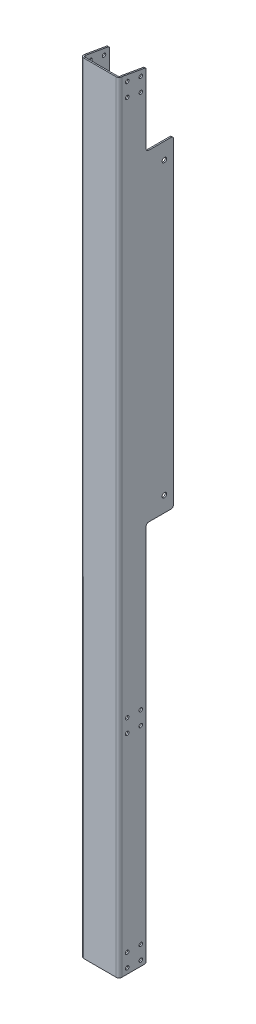
SolidWorks part; units mm, degrees
note: The reader was unsure of these and kept them because the rebuilt part matched: flange length of "Edge-Flange1", "Edge-Flange2".
ref_plane "Front Plane" through (0, 0, 0) normal (0, 0, 1) x (1, 0, 0)
ref_plane "Top Plane" through (0, 0, 0) normal (0, 1, 0) x (1, 0, 0)
ref_plane "Right Plane" through (0, 0, 0) normal (1, 0, 0) x (0, 0, -1)
sketch "Sketch1" plane through (0, 0, 0) normal (0, 0, 1) x (1, 0, 0)
  line L1 (26.6776, 546.1) -> (-26.6776, 546.1)
  line L2 (26.6776, 546.1) -> (26.6776, -546.1)
  line L3 (26.6776, -546.1) -> (-26.6776, -546.1)
  line L4 (-26.6776, 546.1) -> (-26.6776, -546.1)
  line L5 (26.6776, 546.1) -> (-26.6776, -546.1) construction
  line L6 (26.6776, -546.1) -> (-26.6776, 546.1) construction
  point P0 (0, 0)
  dimension "D1" = 53.3552
  dimension "D2" = 1092.2
base flange "Base-Flange1" sketch "Sketch1" thickness 1.8974 reverse thickness direction no parameters "D1"=2.032
edge flange "Edge-Flange1" sketch "Sketch8" flange angle 90 flange length 76.2 flange position material inside bend radius 2.032 thickness 1.8974 relief rectangular parameters "D6"=10
sketch "Sketch8" plane through (26.6776, 0, -1.8974) normal (-1, 0, 0) x (0, 1, 0)
  line L0 (546.1, 2.8778) -> (540.2239, 36.2026)
  line L2 (-546.1, 0) -> (-546.1, 36.2026)
  line L3 (-546.1, 36.2026) -> (-15.875, 36.2026)
  line L4 (546.1, 2.8778) -> (546.1, 0)
  line L5 (546.1, 0) -> (-546.1, 0) construction
  line L6 (546.1, 0) -> (-546.1, 0)
  line L7 (438.15, 39.3776) -> (438.15, 71.1276)
  line L8 (434.975, 74.3026) -> (-9.525, 74.3026)
  line L9 (-12.7, 71.1276) -> (-12.7, 39.3776)
  line L10 (441.325, 36.2026) -> (540.2239, 36.2026)
  line L11 (546.1, -1.8974) -> (-546.1, -1.8974) construction
  arc A0 (-12.7, 39.3776) -> (-15.875, 36.2026) centre (-15.875, 39.3776) cw
  arc A1 (438.15, 39.3776) -> (441.325, 36.2026) centre (441.325, 39.3776) ccw
  arc A2 (-9.525, 74.3026) -> (-12.7, 71.1276) centre (-9.525, 71.1276) ccw
  arc A3 (438.15, 71.1276) -> (434.975, 74.3026) centre (434.975, 71.1276) ccw
  point P17 (438.15, 36.2026)
  dimension "D7" = 3.175
  dimension "D8" = 3.175
  dimension "D9" = 3.175
  dimension "D10" = 3.175
  dimension "D1" = 38.1
  dimension "D2" = 10
  dimension "D3" = 4.7752
  dimension "D4" = 76.2
  dimension "D5" = 533.4
  dimension "D6" = 984.25
bend "EdgeBend1" bend radius 2.032 bend angle 90 parameters "D5"=1
edge flange "Edge-Flange2" sketch "Sketch11" flange angle 90 flange length 76.2 flange position material inside bend radius 2.032 thickness 1.8974 relief rectangular parameters "D6"=10
sketch "Sketch11" plane through (-26.6776, 0, -1.8974) normal (1, 0, 0) x (0, -1, 0)
  line L0 (-546.1, 2.8778) -> (-540.2239, 36.2026)
  line L2 (-546.1, 0) -> (-546.1, 2.8778)
  line L3 (-540.2239, 36.2026) -> (-441.325, 36.2026)
  line L4 (546.1, 36.2026) -> (546.1, 0)
  line L5 (546.1, 0) -> (-546.1, 0) construction
  line L6 (546.1, 0) -> (-546.1, 0)
  line L7 (-438.15, 39.3776) -> (-438.15, 71.1276)
  line L8 (-434.975, 74.3026) -> (9.525, 74.3026)
  line L9 (12.7, 71.1276) -> (12.7, 39.3776)
  line L10 (15.875, 36.2026) -> (546.1, 36.2026)
  line L11 (546.1, -1.8974) -> (-546.1, -1.8974) construction
  arc A0 (-434.975, 74.3026) -> (-438.15, 71.1276) centre (-434.975, 71.1276) ccw
  arc A1 (-438.15, 39.3776) -> (-441.325, 36.2026) centre (-441.325, 39.3776) cw
  arc A2 (12.7, 71.1276) -> (9.525, 74.3026) centre (9.525, 71.1276) ccw
  arc A3 (15.875, 36.2026) -> (12.7, 39.3776) centre (15.875, 39.3776) cw
  point P20 (12.7, 36.2026)
  dimension "D7" = 3.175
  dimension "D8" = 3.175
  dimension "D9" = 3.175
  dimension "D10" = 3.175
  dimension "D1" = 10
  dimension "D2" = 4.7752
  dimension "D3" = 38.1
  dimension "D4" = 984.25
  dimension "D5" = 533.4
  dimension "D6" = 76.2
bend "EdgeBend2" bend radius 2.032 bend angle 90 parameters "D5"=2
fillet "Fillet1" radius 2.54 4 edges at (25.7289, -546.1, -38.1) (-25.7289, 540.2239, -38.1) (-25.7289, -546.1, -38.1) (25.7289, 540.2239, -38.1)
sketch "Sketch12" plane through (-26.6776, 0, 0) normal (-1, 0, 0) x (0, 0, 1)
  line L0 (-38.1, 441.325) -> (-38.1, 538.0926) construction
  line L1 (-3.9294, -546.1) -> (-35.56, -546.1) construction
  circle A0 centre (-30.48, -538.48) radius 2.4638
  circle A1 centre (-30.48, -519.43) radius 2.4638
  circle A2 centre (-11.43, -519.43) radius 2.4638
  circle A3 centre (-11.43, -538.48) radius 2.4638
  dimension "D1" = 4.9276
  dimension "D2" = 7.62
  dimension "D3" = 19.05
  dimension "D4" = 7.62
  dimension "D5" = 19.05
extrude "Cut-Extrude1" cut sketch "Sketch12" against normal through all normal cut yes
sketch "Sketch13" plane through (-26.6776, 0, 0) normal (-1, 0, 0) x (0, 0, 1)
  line L0 (-30.48, 533.2626) -> (-11.43, 536.6216) construction
  line L1 (-11.43, 536.6216) -> (-11.43, 517.2777) construction
  line L2 (-11.43, 517.2777) -> (-30.48, 513.9187) construction
  line L3 (-30.48, 513.9187) -> (-30.48, 533.2626) construction
  line L4 (-36.0011, 540.594) -> (-4.7752, 546.1) construction
  line L5 (-38.1, 441.325) -> (-38.1, 538.0926) construction
  circle A0 centre (-30.48, 533.2626) radius 2.4638
  circle A1 centre (-11.43, 536.6216) radius 2.4638
  circle A2 centre (-11.43, 517.2777) radius 2.4638
  circle A3 centre (-30.48, 513.9187) radius 2.4638
  dimension "D1" = 4.9276
  dimension "D2" = 7.62
  dimension "D3" = 19.05
  dimension "D4" = 8.1788
  dimension "D5" = 19.05
extrude "Cut-Extrude2" cut sketch "Sketch13" against normal through all normal cut yes
sketch "Sketch14" plane through (26.6776, 0, 0) normal (1, 0, 0) x (0, 0, -1)
  line L0 (38.1, -15.875) -> (38.1, -543.56) construction
  line L1 (35.56, -546.1) -> (3.9294, -546.1) construction
  circle A0 centre (11.43, -234.95) radius 2.4638
  circle A1 centre (11.43, -254) radius 2.4638
  circle A2 centre (30.48, -254) radius 2.4638
  circle A3 centre (30.48, -234.95) radius 2.4638
  dimension "D1" = 7.62
  dimension "D4" = 4.9276
  dimension "D2" = 19.05
  dimension "D3" = 19.05
  dimension "D5" = 292.1
extrude "Cut-Extrude3" cut sketch "Sketch14" against normal through all normal cut yes
hole_wizard "E (0.25) Diameter Hole1" positions "Sketch15" profile "Sketch16" hole size "E" standard "ANSI Inch" end condition through all
sketch "Sketch15" plane through (26.6776, 0, 0) normal (1, 0, 0) x (0, 0, -1)
  line L0 (76.2, 434.975) -> (76.2, -9.525) construction
  line L1 (73.025, -12.7) -> (41.275, -12.7) construction
  point P0 (63.5, 415.29)
  point P2 (63.5, 8.89)
  dimension "D1" = 12.7
  dimension "D2" = 21.59
  dimension "D3" = 406.4
sketch "Sketch16" plane through (26.6776, 415.29, -63.5) normal (0, 1, 0) x (0, 0, -1)
  line L0 (0, 0) -> (0, 53.3552)
  line L1 (0, 53.3552) -> (3.175, 53.3552)
  line L2 (3.175, 53.3552) -> (3.175, 0)
  line L5 (3.175, 0) -> (0, 0)
  line L11 (0, -6.35) -> (0, 107.95) construction
  dimension "Thru Hole Dia." = 6.35
  dimension "Thru Hole Depth" = 53.3552
sketch "Bend-Lines1" [suppressed] plane through (0, 0, 0) normal (0, 1, 0) x (1, 0, 0)
sketch "Bounding-Box1" [suppressed] plane through (0, 0, 0) normal (0, 1, 0) x (1, 0, 0)
sheet metal parameters "Sheet-Metal1" thickness 1.8974 parameters "D1"=2.032
flat pattern "Flat-Pattern1" [suppressed]
sketch "Bend-Lines2" plane through (0, 0, 0) normal (0, 1, 0) x (1, 0, 0)
sketch3d "Bounding-Box2" [suppressed]
  line L0 (-26.6776, 508, 0) -> (-26.6776, -508, 0) construction
  line L1 (26.6776, 508, 0) -> (26.6776, -508, 0) construction
  line L2 (-26.6776, 508, 0) -> (26.6776, 508, 0) construction
  line L3 (-26.6776, -508, 0) -> (26.6776, -508, 0) construction
sheet metal parameters "Sheet-Metal2" thickness 1.8974 parameters "D1"=2.032
flat pattern "Flat-Pattern1"
sketch "Bend-Lines2" plane through (0, 0, 0) normal (0, 0, 1) x (1, 0, 0)
  line L0 (25.0893, -508) -> (25.0893, 508) construction
  line L1 (25.0893, -508) -> (25.0893, 508) construction
sketch3d "Bounding-Box2" [suppressed]
  line L0 (61.6009, 508, 0) -> (61.6009, -508, 0) construction
  line L1 (-26.6776, 508, 0) -> (-26.6776, -508, 0) construction
  line L2 (61.6009, 508, 0) -> (-26.6776, 508, 0) construction
  line L3 (61.6009, -508, 0) -> (-26.6776, -508, 0) construction
bend of the flat pattern "Flatten-<EdgeBend1>1"
sheet metal parameters "Sheet-Metal3" thickness 1.8974 parameters "D1"=2.032
flat pattern "Flat-Pattern1"
sketch "Bend-Lines2" plane through (0, 0, 0) normal (0, 0, 1) x (1, 0, 0)
  line L0 (25.0893, -508) -> (25.0893, 508) construction
  line L1 (25.0893, -508) -> (25.0893, 508) construction
  line L2 (-25.0893, 508) -> (-25.0893, -508) construction
  line L3 (-25.0893, 508) -> (-25.0893, -508) construction
sketch3d "Bounding-Box2" [suppressed]
  line L0 (61.6008, -508, 0) -> (61.6009, 513.389, 0) construction
  line L1 (-61.6009, -508, 0) -> (-61.6008, 513.389, 0) construction
  line L2 (61.6008, -508, 0) -> (-61.6009, -508, 0) construction
  line L3 (61.6009, 513.389, 0) -> (-61.6008, 513.389, 0) construction
bend of the flat pattern "Flatten-<EdgeBend1>1"
bend of the flat pattern "Flatten-<EdgeBend2>1"
sheet metal parameters "Sheet-Metal4" thickness 1.8974 parameters "D1"=2.032
flat pattern "Flat-Pattern1"
sketch "Bend-Lines2" plane through (0, 0, 0) normal (0, 0, 1) x (1, 0, 0)
  line L0 (25.0893, -508) -> (25.0893, 508) construction
  line L1 (25.0893, -508) -> (25.0893, 508) construction
  line L2 (-25.0893, 508) -> (-25.0893, -508) construction
  line L3 (-25.0893, 508) -> (-25.0893, -508) construction
sketch3d "Bounding-Box2" [suppressed]
  line L0 (61.6008, -508, 0) -> (61.6009, 513.389, 0) construction
  line L1 (-61.6009, -508, 0) -> (-61.6008, 513.389, 0) construction
  line L2 (61.6008, -508, 0) -> (-61.6009, -508, 0) construction
  line L3 (61.6009, 513.389, 0) -> (-61.6008, 513.389, 0) construction
bend of the flat pattern "Flatten-<EdgeBend1>1"
bend of the flat pattern "Flatten-<EdgeBend2>1"
sheet metal parameters "Sheet-Metal5" thickness 1.8974 parameters "D1"=2.032
flat pattern "Flat-Pattern1"
sketch "Bend-Lines2" plane through (0, 0, 0) normal (0, 0, 1) x (1, 0, 0)
  line L0 (25.0893, -590.042) -> (25.0893, 590.042) construction
  line L1 (25.0893, -590.042) -> (25.0893, 590.042) construction
  line L2 (-25.0893, 590.042) -> (-25.0893, -590.042) construction
  line L3 (-25.0893, 590.042) -> (-25.0893, -590.042) construction
sketch3d "Bounding-Box2" [suppressed]
  line L0 (61.6005, -590.042, 0) -> (61.6009, 590.042, 0) construction
  line L1 (-61.6009, -590.042, 0) -> (-61.6005, 590.042, 0) construction
  line L2 (61.6005, -590.042, 0) -> (-61.6009, -590.042, 0) construction
  line L3 (61.6009, 590.042, 0) -> (-61.6005, 590.042, 0) construction
bend of the flat pattern "Flatten-<EdgeBend1>1"
bend of the flat pattern "Flatten-<EdgeBend2>1"
sheet metal parameters "Sheet-Metal6" thickness 1.8974 parameters "D1"=2.032
flat pattern "Flat-Pattern1"
sketch "Bend-Lines2" plane through (0, 0, 0) normal (0, 0, 1) x (1, 0, 0)
  line L0 (25.0893, -546.1) -> (25.0893, 546.1) construction
  line L1 (25.0893, -546.1) -> (25.0893, 546.1) construction
  line L2 (-25.0893, 546.1) -> (-25.0893, -546.1) construction
  line L3 (-25.0893, 546.1) -> (-25.0893, -546.1) construction
sketch3d "Bounding-Box2" [suppressed]
  line L0 (99.7009, 546.1, 0) -> (99.7009, -546.1, 0) construction
  line L1 (-99.7009, 546.1, 0) -> (-99.7009, -546.1, 0) construction
  line L2 (99.7009, 546.1, 0) -> (-99.7009, 546.1, 0) construction
  line L3 (99.7009, -546.1, 0) -> (-99.7009, -546.1, 0) construction
bend of the flat pattern "Flatten-<EdgeBend1>1"
bend of the flat pattern "Flatten-<EdgeBend2>1"
sheet metal parameters "Sheet-Metal7" thickness 1.8974 parameters "D1"=2.032
flat pattern "Flat-Pattern1"
sketch "Bend-Lines2" plane through (0, 0, 0) normal (0, 0, 1) x (1, 0, 0)
  line L0 (25.0893, -546.1) -> (25.0893, 546.1) construction
  line L1 (25.0893, -546.1) -> (25.0893, 546.1) construction
  line L2 (-25.0893, 546.1) -> (-25.0893, -546.1) construction
  line L3 (-25.0893, 546.1) -> (-25.0893, -546.1) construction
sketch3d "Bounding-Box2" [suppressed]
  line L0 (99.7009, 546.1, 0) -> (99.7009, -546.1, 0) construction
  line L1 (-99.7009, 546.1, 0) -> (-99.7009, -546.1, 0) construction
  line L2 (99.7009, 546.1, 0) -> (-99.7009, 546.1, 0) construction
  line L3 (99.7009, -546.1, 0) -> (-99.7009, -546.1, 0) construction
bend of the flat pattern "Flatten-<EdgeBend1>1"
bend of the flat pattern "Flatten-<EdgeBend2>1"
